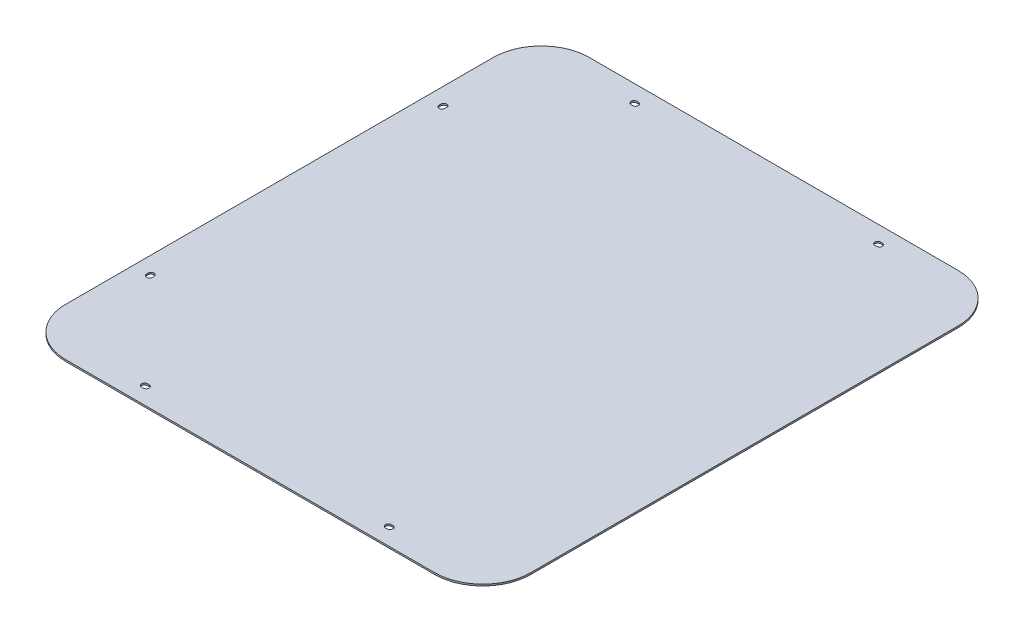
SolidWorks part; units mm, degrees
note: The reader was unsure of these and kept them because the rebuilt part matched: thickness of "Базовая кромка1", "Листовой металл1", "Листовой металл5", "Листовой металл6".
ref_plane "Спереди" through (0, 0, 0) normal (0, 0, 1) x (1, 0, 0)
ref_plane "Сверху" through (0, 0, 0) normal (0, 1, 0) x (1, 0, 0)
ref_plane "Справа" through (0, 0, 0) normal (1, 0, 0) x (0, 0, -1)
sketch "Эскиз1" plane through (0, 0, 0) normal (0, 1, 0) x (1, 0, 0)
  line L1 (-113.5, -161) -> (113.5, -161)
  line L2 (-143, -131.5) -> (-143, 131.5)
  line L3 (-113.5, 161) -> (113.5, 161)
  line L4 (143, -131.5) -> (143, 131.5)
  line L5 (-143, -161) -> (143, 161) construction
  line L6 (-143, 161) -> (143, -161) construction
  arc A0 (-113.5, -161) -> (-143, -131.5) centre (-113.5, -131.5) cw
  arc A1 (143, -131.5) -> (113.5, -161) centre (113.5, -131.5) cw
  arc A2 (143, 131.5) -> (113.5, 161) centre (113.5, 131.5) ccw
  arc A3 (-143, 131.5) -> (-113.5, 161) centre (-113.5, 131.5) cw
  point P0 (0, 0)
  dimension "D3" = 29.5
  dimension "D1" = 322
  dimension "D2" = 286
base flange "Базовая кромка1" sketch "Эскиз1" thickness 1 reverse thickness direction no parameters "D1"=2
sketch "Эскиз2" plane through (0, 0, 0) normal (0, 1, 0) x (1, 0, 0)
  line L0 (74.5, -150.5) -> (75.5, -150.5) construction
  line L1 (74.5, -148.7) -> (75.5, -148.7)
  line L2 (74.5, -152.3) -> (75.5, -152.3)
  line L3 (0, 161) -> (0, -161) construction
  line L4 (113.5, 161) -> (-113.5, 161) construction
  line L5 (-113.5, -161) -> (113.5, -161) construction
  line L6 (-143, 0) -> (143, 0) construction
  line L7 (-143, 131.5) -> (-143, -131.5) construction
  line L8 (143, -131.5) -> (143, 131.5) construction
  line L9 (0, -149.75) -> (128.9001, -149.75)
  line L10 (-74.5, -150.5) -> (-75.5, -150.5) construction
  line L13 (-74.5, -148.7) -> (-75.5, -148.7)
  line L16 (-74.5, -152.3) -> (-75.5, -152.3)
  line L19 (74.5, 150.5) -> (75.5, 150.5) construction
  line L20 (74.5, 148.7) -> (75.5, 148.7)
  line L21 (74.5, 152.3) -> (75.5, 152.3)
  line L22 (-74.5, 150.5) -> (-75.5, 150.5) construction
  line L23 (-74.5, 148.7) -> (-75.5, 148.7)
  line L24 (-74.5, 152.3) -> (-75.5, 152.3)
  line L25 (75, -150.5) -> (75, -149.75)
  arc A0 (74.5, -148.7) -> (74.5, -152.3) centre (74.5, -150.5) ccw
  arc A1 (75.5, -152.3) -> (75.5, -148.7) centre (75.5, -150.5) ccw
  arc A8 (-74.5, -148.7) -> (-74.5, -152.3) centre (-74.5, -150.5) cw
  arc A9 (-75.5, -152.3) -> (-75.5, -148.7) centre (-75.5, -150.5) cw
  arc A10 (74.5, 148.7) -> (74.5, 152.3) centre (74.5, 150.5) cw
  arc A11 (75.5, 152.3) -> (75.5, 148.7) centre (75.5, 150.5) cw
  arc A12 (-74.5, 148.7) -> (-74.5, 152.3) centre (-74.5, 150.5) ccw
  arc A13 (-75.5, 152.3) -> (-75.5, 148.7) centre (-75.5, 150.5) ccw
  point P2 (75, -150.5)
  point P24 (-75, -150.5)
  point P31 (75, 150.5)
  point P38 (-75, 150.5)
  dimension "D3" = 1.8
  dimension "D2" = 1
extrude "Вырез-Вытянуть1" cut sketch "Эскиз2" against normal blind 10 contours A1 L1 A0 L2 | A8 L16 A9 L13 | A11 L20 A10 L21 | A12 L24 A13 L23 normal cut yes
sketch "Эскиз3" plane through (0, -1, 0) normal (0, -1, 0) x (1, 0, 0)
  line L0 (-132.5, 90) -> (-132.5, -24.1919)
  line L1 (-132.5, 89.5) -> (-132.5, 90.5) construction
  line L2 (-134.3, 89.5) -> (-134.3, 90.5)
  line L3 (-130.7, 89.5) -> (-130.7, 90.5)
  line L4 (-143, 0) -> (143, 0) construction
  line L7 (-143, -131.5) -> (-143, 131.5) construction
  line L12 (143, 131.5) -> (143, -131.5) construction
  line L13 (-132.5, -89.5) -> (-132.5, -90.5) construction
  line L14 (-134.3, -89.5) -> (-134.3, -90.5)
  line L15 (-130.7, -89.5) -> (-130.7, -90.5)
  arc A0 (-134.3, 89.5) -> (-130.7, 89.5) centre (-132.5, 89.5) ccw
  arc A1 (-130.7, 90.5) -> (-134.3, 90.5) centre (-132.5, 90.5) ccw
  arc A6 (-134.3, -89.5) -> (-130.7, -89.5) centre (-132.5, -89.5) cw
  arc A7 (-130.7, -90.5) -> (-134.3, -90.5) centre (-132.5, -90.5) cw
  point P5 (-132.5, 90)
  point P18 (-132.5, -90)
  dimension "D2" = 1.8
  dimension "D1" = 1
  dimension "D3" = 0
extrude "Вырез-Вытянуть2" cut sketch "Эскиз3" against normal blind 10 contours A1 L2 A0 L3 | A6 L15 A7 L14 normal cut yes
sketch "Сгиб-Линии1" [suppressed] plane through (0, 0, 0) normal (0, 1, 0) x (1, 0, 0)
sketch "Граничная рамка1" [suppressed] plane through (0, 0, 0) normal (0, 1, 0) x (1, 0, 0)
sheet metal parameters "Листовой металл1" thickness 1 parameters "D1"=2
flat pattern "Развертка1" [suppressed]
sketch "Сгиб-Линии2" plane through (0, 0, 0) normal (0, 1, 0) x (1, 0, 0)
sketch3d "Граничная рамка2" [suppressed]
  line L0 (255, -30, 0) -> (255, 291, 0) construction
  line L1 (-30, -30, 0) -> (-30, 291, 0) construction
  line L2 (255, -30, 0) -> (-30, -30, 0) construction
  line L3 (255, 291, 0) -> (-30, 291, 0) construction
sheet metal parameters "Листовой металл5" thickness 1 parameters "D1"=2, "D7"=1.5
flat pattern "Развертка1"
sketch "Сгиб-Линии2" plane through (0, 0, 0) normal (0, 1, 0) x (1, 0, 0)
sketch3d "Граничная рамка2" [suppressed]
  line L0 (255, -30, 0) -> (255, 291, 0) construction
  line L1 (-30, -30, 0) -> (-30, 291, 0) construction
  line L2 (255, -30, 0) -> (-30, -30, 0) construction
  line L3 (255, 291, 0) -> (-30, 291, 0) construction
sheet metal parameters "Листовой металл6" thickness 1 parameters "D1"=2, "D7"=1.5
flat pattern "Развертка1"
sketch "Сгиб-Линии2" plane through (0, 0, 0) normal (0, 1, 0) x (1, 0, 0)
sketch3d "Граничная рамка2" [suppressed]
  line L0 (256.5, -29.5, 0) -> (256.5, 292.5, 0) construction
  line L1 (-29.5, -29.5, 0) -> (-29.5, 292.5, 0) construction
  line L2 (256.5, -29.5, 0) -> (-29.5, -29.5, 0) construction
  line L3 (256.5, 292.5, 0) -> (-29.5, 292.5, 0) construction
